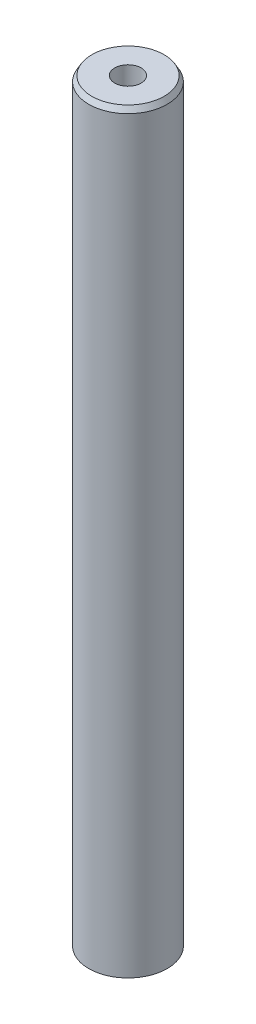
SolidWorks part; units mm, degrees
ref_plane "Front Plane" through (0, 0, 0) normal (0, 0, 1) x (1, 0, 0)
ref_plane "Top Plane" through (0, 0, 0) normal (0, 1, 0) x (1, 0, 0)
ref_plane "Right Plane" through (0, 0, 0) normal (1, 0, 0) x (0, 0, -1)
sketch "Sketch1" plane through (0, 0, 0) normal (0, 1, 0) x (1, 0, 0)
  circle A0 centre (0, 0) radius 12.5
  dimension "SHAFT_OD" = 25
extrude "Boss-Extrude1" add sketch "Sketch1" along normal blind 241.2552
sketch "Sketch2" plane through (0, 0, 0) normal (0, 1, 0) x (1, 0, 0)
  circle A0 centre (0, 0) radius 4.2046
  dimension "BORE_D" = 8.4092
extrude "Cut-Extrude1" cut sketch "Sketch2" along normal through all
chamfer "Chamfer1" distance 1.7063 angle 30 2 edges at (0, 241.2552, 12.5) (0, 0, 12.5) first distance on face at (0, 241.2552, 12.5) first distance on face at (0, 0, 4.2046)
